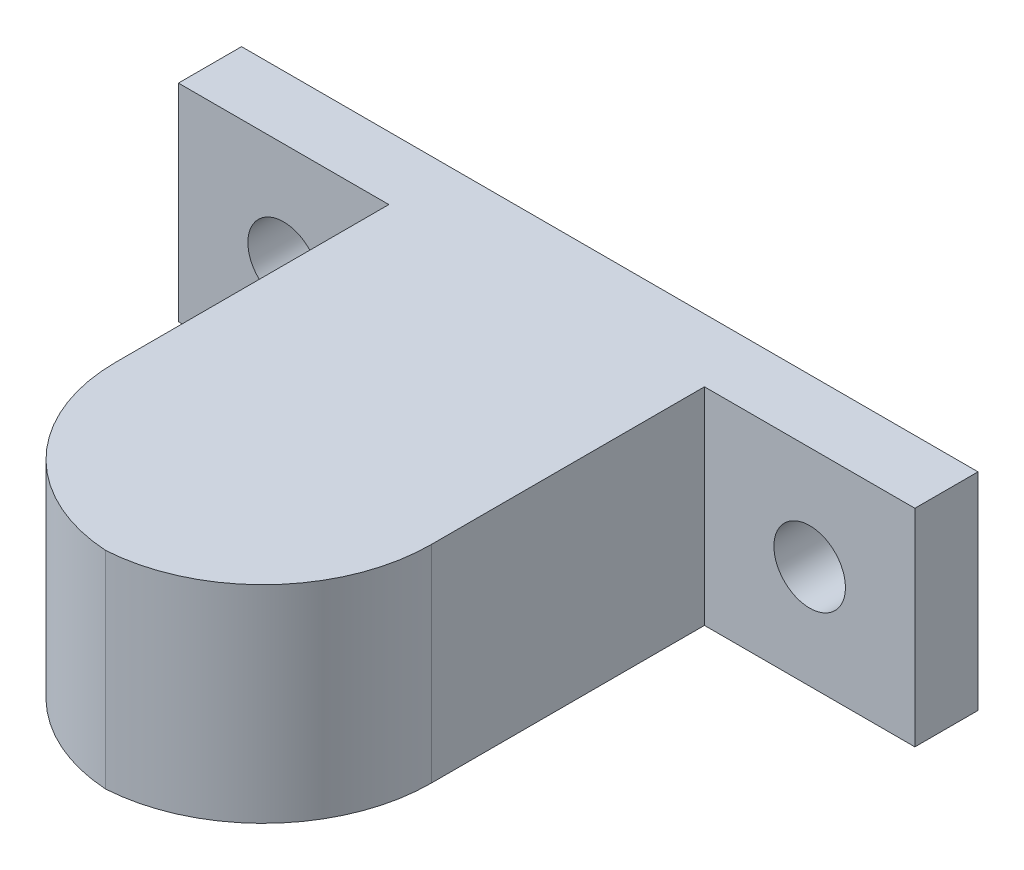
SolidWorks part; units mm, degrees
material "Custom Plastic"
ref_plane "Front Plane" through (0, 0, 0) normal (0, 0, 1) x (1, 0, 0)
ref_plane "Top Plane" through (0, 0, 0) normal (0, 1, 0) x (1, 0, 0)
ref_plane "Right Plane" through (0, 0, 0) normal (1, 0, 0) x (0, 0, -1)
sketch "Sketch1" plane through (0, 0, 0) normal (0, 0, 1) x (1, 0, 0)
  line L0 (-271.35, 25) -> (-271.35, 0) construction
  line L1 (-271.35, 25) -> (-271.35, 0) construction
  line L2 (-236.35, 25) -> (-236.35, 0) construction
  line L3 (-236.35, 25) -> (-236.35, 0) construction
  line L4 (-241.35, 19) -> (-241.35, -49981) construction
  line L5 (-266.35, 19) -> (-266.35, 50019) construction
  line L6 (-304.8, 304.8) -> (0, 304.8) construction
  line L7 (-271.35, 304.6227) -> (-236.35, 304.6227)
  line L8 (-109.7919, 304.6227) -> (-109.7919, 259.2066)
  line L9 (-109.7919, 259.2066) -> (-195.0081, 259.2066)
  line L10 (-195.0081, 259.2066) -> (-195.0081, 304.6227)
  line L11 (-195.0081, 304.6227) -> (-304.8, 304.6227)
  line L12 (-304.8, 304.6227) -> (-304.8, 0)
  line L13 (-304.8, 0) -> (0, 0)
  line L14 (0, 0) -> (0, 304.6227)
  line L15 (0, 304.6227) -> (-109.7919, 304.6227)
  line L16 (-109.7919, 304.6227) -> (-109.7919, 259.2066)
  line L17 (-109.7919, 259.2066) -> (-195.0081, 259.2066)
  line L18 (-195.0081, 259.2066) -> (-195.0081, 304.6227)
  line L19 (-195.0081, 304.6227) -> (-304.8, 304.6227)
  line L20 (-304.8, 304.6227) -> (-304.8, 0)
  line L21 (-304.8, 0) -> (0, 0)
  line L22 (0, 0) -> (0, 304.6227)
  line L23 (0, 304.6227) -> (-109.7919, 304.6227)
  line L24 (-271.35, 304.6227) -> (-271.35, 294.8)
  line L26 (-236.35, 304.6227) -> (-236.35, 294.8)
  line L27 (-269.8, 294.8) -> (-234.8, 294.8) construction
  line L28 (-304.8, 304.8) -> (0, 304.8)
  line L29 (-269.8, 294.8) -> (-236.35, 294.8)
  line L30 (-271.35, 294.8) -> (-236.35, 294.8)
  line L31 (-266.35, 304.6227) -> (-266.35, 294.8)
  line L32 (-241.35, 304.6227) -> (-241.35, 294.8)
  circle A0 centre (-266.35, 19) radius 1.7 construction
  circle A1 centre (-266.35, 19) radius 1.7
  circle A2 centre (-266.35, 6) radius 1.7 construction
  circle A3 centre (-266.35, 6) radius 1.7
  circle A4 centre (-241.35, 6) radius 1.7 construction
  circle A5 centre (-241.35, 19) radius 1.7 construction
  circle A6 centre (-241.35, 6) radius 1.7
  circle A7 centre (-241.35, 19) radius 1.7
  circle A8 centre (-266.35, 299.7114) radius 1.7
  circle A9 centre (-241.35, 299.7114) radius 1.7
  dimension "D1" = 0
extrude "Boss-Extrude1" add sketch "Sketch1" along normal blind 3 contours A9 L32 L19 L31 A8 L30 | A8 L31 L7 L24 L30 L29 | A9 L32 L29 L26 L7 region at (-269.0311, 299.7114, 0) region at (-253.85, 299.7114, 0) region at (-238.6689, 299.7114, 0)
sketch "Sketch2" plane through (0, 304.6227, 0) normal (0, 1, 0) x (1, 0, 0)
  line L3 (-246.35, -28) -> (-246.35, -5) construction
  line L4 (-261.35, -5) -> (-261.35, -15) construction
  line L5 (-246.35, -28) -> (-246.35, -5)
  line L6 (-261.35, -5) -> (-261.35, -15)
  line L12 (-261.35, -2.8334) -> (-246.35, -2.8334)
  line L17 (-261.35, -2.8334) -> (-261.35, -23.9809)
  line L18 (-261.35, -23.9809) -> (-246.35, -23.9809)
  line L19 (-246.35, -2.8334) -> (-246.35, -23.9809)
  circle A1 centre (-253.85, -16.5) radius 4
  circle A2 centre (-253.85, -16.5) radius 4
  dimension "D1" = 0
extrude "Boss-Extrude2" add sketch "Sketch2" against normal up to surface (9.8227 mm away) contours L17 L12 L19 L18 up to face at (-253.85, 294.8, 1.5)
fillet "Fillet1" radius 8 2 edges at (-246.35, 299.7114, 23.9809) (-261.35, 299.7114, 23.9809)
sketch "Sketch3" plane through (0, 294.8, 0) normal (0, -1, 0) x (1, 0, 0)
  circle A4 centre (-253.85, 16.5) radius 4.1
extrude "Cut-Extrude1" cut sketch "Sketch3" against normal up to surface (7.2 mm away)
